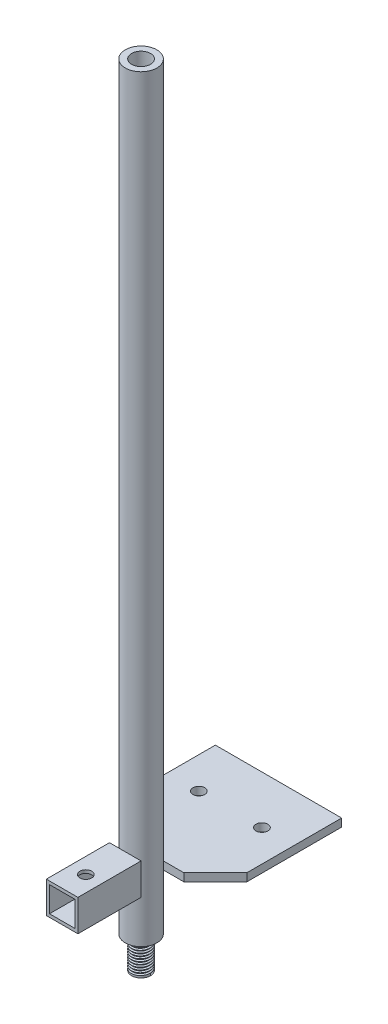
SolidWorks part; units mm, degrees
ref_plane "Front Plane" through (0, 0, 0) normal (0, 0, 1) x (1, 0, 0)
ref_plane "Top Plane" through (0, 0, 0) normal (0, 1, 0) x (1, 0, 0)
ref_plane "Right Plane" through (0, 0, 0) normal (1, 0, 0) x (0, 0, -1)
sketch "Sketch1" plane through (0, 0, 0) normal (0, 1, 0) x (1, 0, 0)
  line L0 (-7.62, 0) -> (-12.7, 0) construction
  circle A0 centre (0, 0) radius 12.7
  circle A1 centre (0, 0) radius 7.62
  dimension "D1" = 25.4
  dimension "D2" = 5.08
extrude "Boss-Extrude1" add sketch "Sketch1" along normal blind 609.6
ref_plane "Plane1" through (0, 12.7, 0) normal (0, -1, 0) x (-1, 0, 0)
sketch "Sketch2" plane through (0, 12.7, 0) normal (0, -1, 0) x (-1, 0, 0)
  circle A0 centre (0, 0) radius 7.62
extrude "Boss-Extrude2" add sketch "Sketch2" along normal blind 38.1
sketch "Sketch5" plane through (0, -25.4, 0) normal (0, -1, 0) x (1, 0, 0)
  circle A0 centre (0, 0) radius 7.62
thread "Thread1" pitch 1.9538 method cut profile "Thread Profile2" start angle 0, offset 0, length 38.1, pitch 1.9538, diameter 15.24
ref_plane "Plane3" through (7.62, -25.4, 0) normal (0, 0, 1) x (1, 0, 0)
sketch "Thread Profile2" plane through (7.62, -25.4, 0) normal (0, 0, 1) x (1, 0, 0)
  line L0 (0, 0) -> (0, 1.9538) construction
  line L11 (0, 0) -> (0, 1.7096)
  line L12 (0, 1.7096) -> (-1.0576, 1.099)
  line L13 (-1.0576, 1.099) -> (-1.0576, 0.6106)
  line L15 (-1.0576, 0.6106) -> (0, 0)
  line L17 (-1.0576, 0.8548) -> (0, 0.8548) construction
  point P2 (0, 0)
  dimension "Pitch" = 1.9538
  dimension "Profile_Angle" = 60
  dimension "Profile_Land" = 0.4885
  dimension "Profile_Height" = 1.0576
ref_plane "Plane4" through (0, 0, 12.7) normal (0, 0, 1) x (1, 0, 0)
ref_plane "Plane5" through (0, 50.8, 0) normal (0, -1, 0) x (-1, 0, 0)
sketch "Sketch10" plane through (0, 50.8, 0) normal (0, -1, 0) x (-1, 0, 0)
  line L0 (0, 0) -> (0, 12.7) construction
  line L1 (-8.9803, 8.9803) -> (0, 0) construction
  line L2 (0, 0) -> (8.9803, 8.9803) construction
  line L3 (-8.9803, 8.9803) -> (-25.4, 8.9803)
  line L4 (-25.4, 8.9803) -> (-50.8, 34.3803)
  line L5 (-50.8, 34.3803) -> (-50.8, 110.5803)
  line L6 (-50.8, 110.5803) -> (50.8, 110.5803)
  line L7 (0, 110.5803) -> (0, 12.7) construction
  line L8 (0, 0) -> (-8.9803, 8.9803) construction
  line L9 (8.9803, 8.9803) -> (0, 0) construction
  line L10 (50.8, 34.3803) -> (50.8, 110.5803)
  line L11 (25.4, 8.9803) -> (50.8, 34.3803)
  line L12 (8.9803, 8.9803) -> (25.4, 8.9803)
  arc A0 (-8.9803, 8.9803) -> (8.9803, 8.9803) centre (0, 0) cw
  circle A1 centre (0, 0) radius 12.7 construction
  dimension "D1" = 45
  dimension "D3" = 101.6
  dimension "D4" = 50.8
  dimension "D5" = 25.4
  dimension "D6" = 25.4
extrude "Boss-Extrude4" add sketch "Sketch10" along normal blind 6.35
sketch "Sketch11" plane through (0, 50.8, 0) normal (0, 1, 0) x (1, 0, 0)
  line L0 (0, 0) -> (0, 71.842) construction
  line L1 (0, 71.842) -> (-25.4, 71.842) construction
  circle A0 centre (-25.4, 71.842) radius 4.7625
  circle A1 centre (25.4, 71.842) radius 4.7625
  dimension "D1" = 9.525
  dimension "D2" = 76.2
  dimension "D3" = 25.4
extrude "Cut-Extrude2" cut sketch "Sketch11" against normal up to next
sketch "Sketch8" plane through (0, 0, 12.7) normal (0, 0, 1) x (1, 0, 0)
  line L0 (0, 0) -> (0, 50.8) construction
  line L1 (12.7, 0) -> (12.7, 609.6) construction
  line L2 (-12.7, 38.1) -> (12.7, 38.1)
  line L3 (-12.7, 38.1) -> (-12.7, 63.5)
  line L4 (-12.7, 63.5) -> (12.7, 63.5)
  line L5 (12.7, 38.1) -> (12.7, 63.5)
  line L6 (-12.7, 38.1) -> (12.7, 63.5) construction
  line L7 (-12.7, 63.5) -> (12.7, 38.1) construction
  line L8 (-10.16, 50.8) -> (-12.7, 50.8) construction
  line L9 (10.16, 40.64) -> (-10.16, 40.64)
  line L10 (10.16, 40.64) -> (10.16, 60.96)
  line L11 (10.16, 60.96) -> (-10.16, 60.96)
  line L12 (-10.16, 40.64) -> (-10.16, 60.96)
  line L13 (10.16, 40.64) -> (-10.16, 60.96) construction
  line L14 (10.16, 60.96) -> (-10.16, 40.64) construction
  dimension "D1" = 50.8
  dimension "D2" = 2.54
extrude "Boss-Extrude3" add sketch "Sketch8" along normal blind 50.8 separate body
sketch "Sketch9" plane through (0, 63.5, 0) normal (0, 1, 0) x (1, 0, 0)
  line L0 (0, 0) -> (0, -44.45) construction
  circle A0 centre (0, -44.45) radius 4.7625
  dimension "D2" = 9.525
  dimension "D1" = 44.45
extrude "Cut-Extrude1" cut sketch "Sketch9" against normal through all
